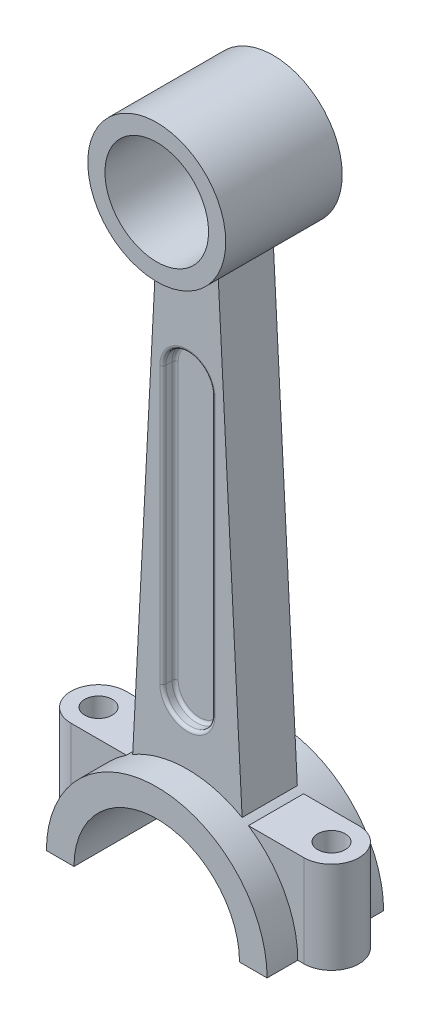
SolidWorks part; units mm, degrees
ref_plane "Front Plane" through (0, 0, 0) normal (0, 0, 1) x (1, 0, 0)
ref_plane "Top Plane" through (0, 0, 0) normal (0, 1, 0) x (1, 0, 0)
ref_plane "Right Plane" through (0, 0, 0) normal (1, 0, 0) x (0, 0, -1)
sketch "Sketch1" plane through (0, 0, 0) normal (0, 0, 1) x (1, 0, 0)
  line L0 (0, 0) -> (0, -201.2) construction
  line L1 (-10, -20.1556) -> (-17.8497, -169.9368)
  line L2 (10, -20.1556) -> (17.8497, -169.9368)
  line L3 (36, -201.2) -> (-36, -201.2)
  circle A0 centre (0, 0) radius 22.5
  circle A1 centre (0, 0) radius 16.9
  arc A2 (27, -201.2) -> (-27, -201.2) centre (0, -201.2) ccw
  arc A3 (36, -201.2) -> (-36, -201.2) centre (0, -201.2) ccw
  dimension "D1" = 45
  dimension "D2" = 33.8
  dimension "D3" = 201.2
  dimension "D4" = 54
  dimension "D5" = 72
  dimension "D6" = 6
  dimension "D7" = 20
extrude "Boss-Extrude1" add sketch "Sketch1" along normal mid plane 38 contours L0 A3 L3 A2 | A3 L0 A2 L3 | A1 A0 | A2 | A1 | A0 region at (-4.9903, -21.2865, 0) region at (20.1899, -181.0101, 0) region at (-20.1899, -181.0101, 0)
extrude "Boss-Extrude2" add sketch "Sketch1<5>" along normal mid plane 18 contours A0 L0 A3 L2 | L0 A0 L1 A3 region at (7.1843, -100.8455, 0) region at (-7.1843, -100.8455, 0)
sketch "Sketch1<5>" plane through (0, 0, 0) normal (0, 0, 1) x (1, 0, 0) same geometry as "Sketch1"
sketch "Sketch2" plane through (0, 0, 9) normal (0, 0, 1) x (1, 0, 0)
  line L0 (0, 0) -> (0, -201.2) construction
  line L1 (0, -145.6) -> (0, -55.6) construction
  line L2 (-8, -145.6) -> (-8, -55.6)
  line L3 (8, -145.6) -> (8, -55.6)
  arc A0 (-8, -145.6) -> (8, -145.6) centre (0, -145.6) ccw
  arc A1 (8, -55.6) -> (-8, -55.6) centre (0, -55.6) ccw
  point P6 (0, -100.6)
  dimension "D2" = 8
  dimension "D1" = 90
extrude "Cut-Extrude1" cut sketch "Sketch2" against normal blind 4
mirror "Mirror1" about plane through (0, 0, 0) normal (0, 0, 1) of "Cut-Extrude1"
fillet "Fillet1" radius 1 16 edges at (0, -153.6, 9) (-8, -100.6, 9) (0, -47.6, 9) (0, -153.6, 5) (-8, -100.6, 5) (0, -47.6, 5) (0, -153.6, -5) (-8, -100.6, -5) (0, -47.6, -5) (0, -153.6, -9) (-8, -100.6, -9) (0, -47.6, -9) (8, -100.6, 9) (8, -100.6, 5) (8, -100.6, -5) (8, -100.6, -9)
ref_plane "Plane1" through (0, -171.2, 0) normal (0, -1, 0) x (-1, 0, 0)
sketch "Sketch3" plane through (0, -171.2, 0) normal (0, -1, 0) x (-1, 0, 0)
  line L1 (38, 0) -> (-38, 0) construction
  line L2 (38, -9) -> (-38, -9)
  line L3 (38, 9) -> (-38, 9)
  arc A0 (38, -9) -> (38, 9) centre (38, 0) ccw
  arc A1 (-38, 9) -> (-38, -9) centre (-38, 0) ccw
  point P1 (0, 0)
  dimension "D2" = 9
  dimension "D1" = 76
extrude "Boss-Extrude3" add sketch "Sketch3" along normal up to surface (30 mm away) up to face at (31.5, -201.2, 0)
sketch "Sketch4" plane through (0, 0, 9) normal (0, 0, 1) x (1, 0, 0)
  line L1 (-27, -201.2) -> (27, -201.2)
  line L2 (-27, -201.2) -> (27, -201.2)
  arc A1 (27, -201.2) -> (-27, -201.2) centre (0, -201.2) ccw
  arc A2 (27, -201.2) -> (-27, -201.2) centre (0, -201.2) ccw
  dimension "D1" = 0
extrude "Cut-Extrude2" cut sketch "Sketch4" against normal through all
sketch "Sketch5" plane through (0, -171.2, 0) normal (0, 1, 0) x (1, 0, 0)
  circle A1 centre (38, 0) radius 4.5
  circle A2 centre (-38, 0) radius 4.5
extrude "Cut-Extrude3" cut sketch "Sketch5" against normal through all
